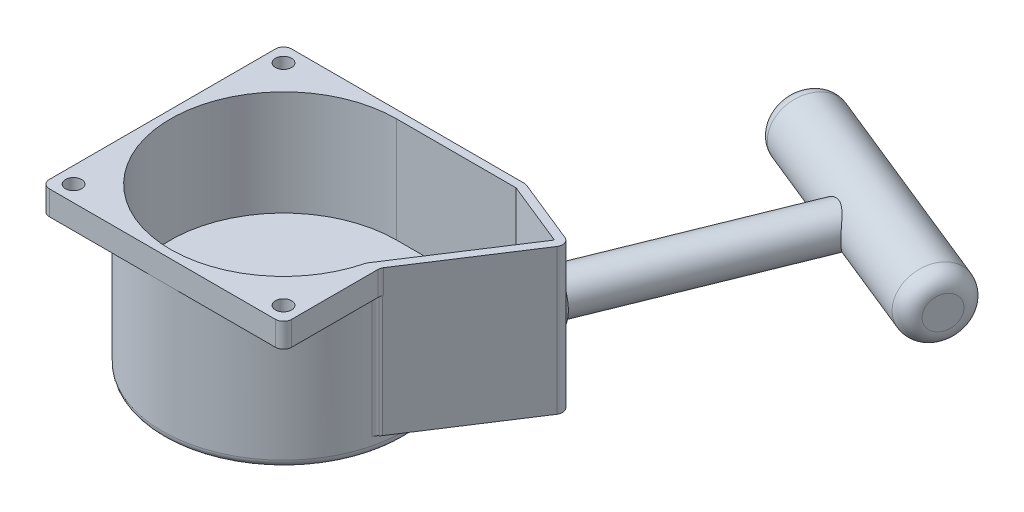
SolidWorks part; units mm, degrees
material "ABS"
ref_plane "Front" through (0, 0, 0) normal (0, 0, 1) x (1, 0, 0)
ref_plane "Top" through (0, 0, 0) normal (0, 1, 0) x (1, 0, 0)
ref_plane "Right" through (0, 0, 0) normal (1, 0, 0) x (0, 0, -1)
sketch "Sketch1" plane through (0, 0, 0) normal (0, 1, 0) x (1, 0, 0)
  circle A0 centre (0, 0) radius 15
extrude "Boss-Extrude1" add sketch "Sketch1" along normal blind 17
sketch "Sketch2" plane through (0, 17, 0) normal (0, 1, 0) x (1, 0, 0)
  line L1 (-15, 15) -> (15, 15)
  line L2 (-15, 15) -> (-15, -15)
  line L3 (-15, -15) -> (15, -15)
  line L4 (15, 15) -> (15, -15)
  line L5 (-15, 15) -> (15, -15) construction
  line L6 (-15, -15) -> (15, 15) construction
  point P0 (0, 0)
  dimension "D1" = 30
  dimension "D2" = 30
extrude "Boss-Extrude2" add sketch "Sketch2" along normal blind 3
fillet "Fillet2" radius 1 1 edges at (0, 0, 15)
sketch "Sketch4" plane through (0, 20, 0) normal (0, 1, 0) x (1, 0, 0)
  line L0 (15, 15) -> (24.2702, 11.25)
  line L1 (24.2702, 11.25) -> (15, -3)
  line L2 (15, -15) -> (15, 15) construction
  line L3 (15, -3) -> (15, 15)
  line L4 (-15, -15) -> (15, -15) construction
  dimension "D1" = 12
  dimension "D2" = 17
  dimension "D3" = 10
extrude "Boss-Extrude4" add sketch "Sketch4" against normal blind 3
sketch "Sketch6" plane through (0, 20, 0) normal (0, 1, 0) x (1, 0, 0)
  line L0 (15, -3) -> (0, -3)
  line L1 (0, -3) -> (0, 15)
  line L2 (15, 15) -> (-15, 15) construction
  line L3 (0, 15) -> (15, 15)
  line L4 (15, 15) -> (24.2702, 11.25)
  line L5 (24.2702, 11.25) -> (15, -3)
extrude "Boss-Extrude5" add sketch "Sketch6" against normal blind 18
fillet "Fillet5" radius 1 6 edges at (-15, 18.5, 15) (-15, 18.5, -15) (15, 11, -15) (24.2702, 11, -11.25) (15, 18.5, 3) (15, 18.5, 15)
fillet "Fillet6" radius 1 1 edges at (14.6969, 9.5, 3)
fillet "Fillet7" radius 1 1 edges at (15, 9.5, 3)
sketch "Sketch7" plane through (0, 20, 0) normal (0, 1, 0) x (1, 0, 0)
  line L0 (0, 14) -> (14.8054, 14)
  line L1 (14.8054, 14) -> (22.7702, 10.7781)
  line L2 (22.7702, 10.7781) -> (13.6017, -3.3156)
  line L3 (15.1618, -2.7513) -> (23.6085, 10.2328) construction
  line L4 (23.1452, 11.7051) -> (15.1804, 14.927) construction
  line L5 (14.8054, 15) -> (-14, 15) construction
  circle A0 centre (0, 0) radius 14
extrude "Cut-Extrude1" cut sketch "Sketch7" against normal blind 13 contours A0 L2 L1 L0 | A0 region at (14.7415, 20, -8.6584) region at (0, 20, 0)
sketch "Sketch8" plane through (7.3239, 0, -18.1051) normal (0.375, 0, -0.927) x (-0.927, 0, -0.375)
  circle A0 centre (-12.7709, 11) radius 3.5
  circle A1 centre (-12.7709, 11) radius 1.5
  dimension "D1" = 7
extrude "Cut-Extrude2" cut sketch "Sketch8" against normal blind 13 contours A1 region at (19.1628, 11, -13.3161)
sketch "Sketch9" plane through (7.3239, 0, -18.1051) normal (0.375, 0, -0.927) x (-0.927, 0, -0.375)
  circle A0 centre (-12.7709, 11) radius 3.5
extrude "Boss-Extrude6" add sketch "Sketch9" along normal blind 1
sketch "Sketch10" plane through (7.3239, 0, -18.1051) normal (-0.375, 0, 0.927) x (0.927, 0, 0.375)
  circle A0 centre (12.7709, 11) radius 1.5
extrude "Cut-Extrude3" cut sketch "Sketch10" against normal blind 1
fillet "Fillet8" radius 1 1 edges at (16.2932, 11, -15.5556)
sketch "Sketch13" plane through (0, 20, 0) normal (0, 1, 0) x (1, 0, 0)
  line L0 (14.8054, 15) -> (-14, 15) construction
  line L1 (-15, 14) -> (-15, -14) construction
  line L2 (-14, -15) -> (14, -15) construction
  line L3 (15, -14) -> (15, -3.2966) construction
  circle A0 centre (-13, 13) radius 1
  circle A1 centre (-13, -13) radius 1
  circle A2 centre (13, -13) radius 1
  dimension "D1" = 2
  dimension "D3" = 2
  dimension "D5" = 2
  dimension "D2" = 2
  dimension "D4" = 2
  dimension "D6" = 2
extrude "Cut-Extrude4" cut sketch "Sketch13" against normal through all
sketch "Sketch14" plane through (7.6989, 0, -19.0322) normal (0.375, 0, -0.927) x (-0.927, 0, -0.375)
  circle A0 centre (-12.7709, 11) radius 2.5
extrude "Boss-Extrude7" add sketch "Sketch14" along normal blind 30
ref_plane "Plane1" through (15.8214, 0, 6.4001) normal (0.927, 0, 0.375) x (0, -1, 0)
sketch "Sketch16" plane through (18.9489, 0, -46.8429) normal (0.375, 0, -0.927) x (-0.927, 0, -0.375)
  line L0 (-12.7709, 11) -> (-12.7709, 8.5) construction
  circle A0 centre (-12.7709, 11) radius 2.5 construction
ref_plane "Plane2" through (11.8389, 0, 4.7891) normal (0.927, 0, 0.375) x (0.375, 0, -0.927)
sketch "Sketch17" plane through (11.8389, 0, 4.7891) normal (0.927, 0, 0.375) x (0.375, 0, -0.927)
  line L0 (50.5304, 8.5) -> (50.5304, 13.5) construction
  circle A0 centre (50.5304, 11) radius 4
extrude "Boss-Extrude8" add sketch "Sketch17" along normal blind 16 and the other way blind 16
fillet "Fillet9" radius 2 2 edges at (17.4554, 11, -51.7619) (47.1202, 11, -39.7619)
